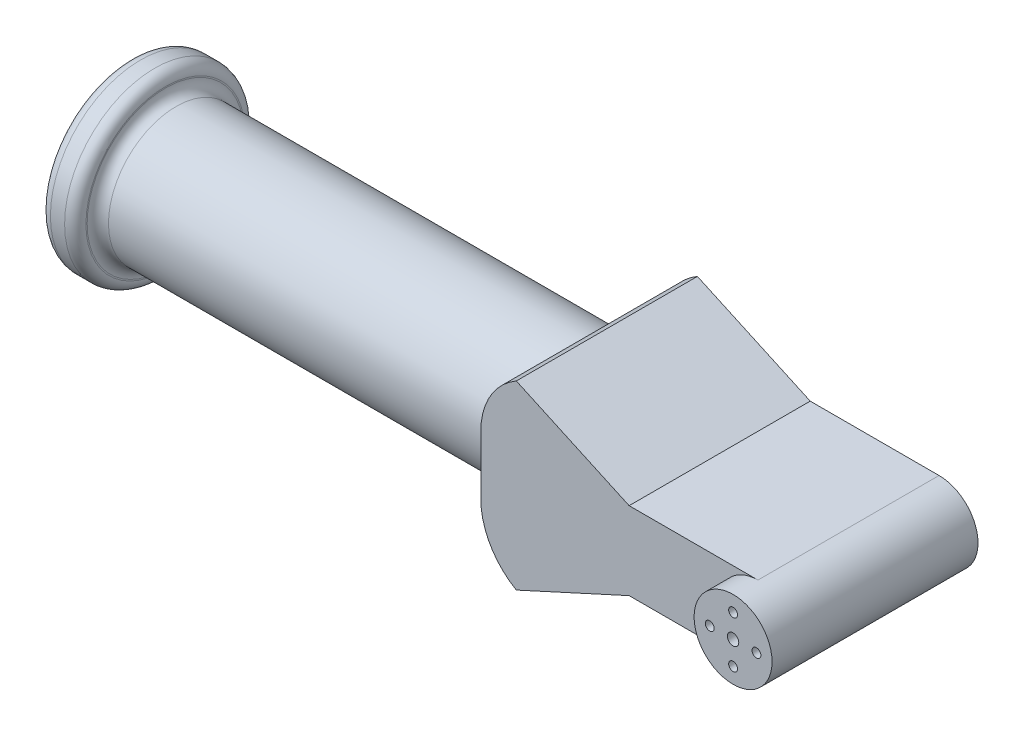
SolidWorks part; units mm, degrees
ref_plane "Front Plane" through (0, 0, 0) normal (0, 0, 1) x (1, 0, 0)
ref_plane "Top Plane" through (0, 0, 0) normal (0, 1, 0) x (1, 0, 0)
ref_plane "Right Plane" through (0, 0, 0) normal (1, 0, 0) x (0, 0, -1)
sketch "Sketch1" plane through (0, 0, 0) normal (1, 0, 0) x (0, 0, -1)
  line L0 (0, 10.97) -> (80, 10.97)
  line L1 (80, 10.97) -> (80, -10.97)
  line L2 (0, -10.97) -> (80, -10.97)
  arc A0 (0, 10.97) -> (0, -10.97) centre (0, 0) ccw
  dimension "D1" = 21.94
  dimension "D2" = 80
extrude "Boss-Extrude1" add sketch "Sketch1" along normal blind 15
sketch "Sketch2" plane through (15, 0, 0) normal (1, 0, 0) x (0, 0, -1)
  line L0 (0, 28.05) -> (0, -28.05) construction
  circle A0 centre (0, 0) radius 10.97
  circle A1 centre (0, 0) radius 1.6
  circle A2 centre (0, 6.58) radius 1.25
  circle A3 centre (6.58, 0) radius 1.25
  circle A4 centre (0, -6.58) radius 1.25
  circle A5 centre (-6.58, 0) radius 1.25
  point P17 (0, 0)
  dimension "D1" = 3.2
  dimension "D2" = 2.5
  dimension "D3" = 6.58
  dimension "D4" = 4
extrude "Boss-Extrude2" add sketch "Sketch2" along normal blind 5.89
sketch "Sketch3" plane through (20.89, 0, 0) normal (1, 0, 0) x (0, 0, -1)
  circle A0 centre (0, 6.58) radius 1.25
  circle A1 centre (0, 0) radius 1.6
  circle A2 centre (0, -6.58) radius 1.25
  circle A3 centre (-6.58, 0) radius 1.25
  circle A4 centre (6.58, 0) radius 1.25
extrude "Cut-Extrude1" cut sketch "Sketch3" against normal blind 100
sketch "Sketch4" plane through (15, 0, 0) normal (1, 0, 0) x (0, 0, -1)
  line L0 (80, 10.97) -> (0, 10.97) construction
  line L1 (30, 10.97) -> (80, 10.97)
  line L2 (30, 10.97) -> (30, -10.97)
  line L3 (30, -10.97) -> (80, -10.97)
  line L4 (80, 10.97) -> (80, -10.97)
  dimension "D1" = 30
extrude "Boss-Extrude3" add sketch "Sketch4" along normal blind 49.02
sketch "Sketch5" plane through (0, 0, 0) normal (0, 1, 0) x (1, 0, 0)
  line L0 (0, -12.067) -> (0, 12.067) construction
  line L1 (64.02, 34.7595) -> (0, 34.7595) construction
  line L2 (64.02, 80) -> (64.02, 30) construction
  line L3 (32.01, 80) -> (32.01, -10.8477) construction
  line L4 (64.02, 80) -> (0, 80) construction
sketch "Sketch6" plane through (0, 10.97, 0) normal (0, 1, 0) x (1, 0, 0)
  line L0 (64.02, 80) -> (0, 80) construction
  line L1 (15, 30) -> (44, 30)
  line L2 (15, 30) -> (15, 80)
  line L3 (15, 80) -> (44, 80)
  line L4 (44, 30) -> (44, 80)
sketch "Sketch9" plane through (0, 0, 0) normal (-1, 0, 0) x (0, 0, 1)
  line L0 (-80, 0) -> (10.8477, 0) construction
  line L1 (-80, 25.5) -> (-29, 25.5)
  line L2 (-80, 25.5) -> (-80, -25.5)
  line L3 (-80, -25.5) -> (-29, -25.5)
  line L4 (-29, 25.5) -> (-29, -25.5)
  line L5 (-80, 25.5) -> (-29, -25.5) construction
  line L6 (-80, -25.5) -> (-29, 25.5) construction
  line L7 (-80, 10.97) -> (-80, -10.97) construction
  point P0 (-54.5, 0)
  dimension "D1" = 29
  dimension "D2" = 25.5
  dimension "D3" = 0
extrude "Boss-Extrude7" add sketch "Sketch9" along normal blind 10
sketch "Sketch10" plane through (-10, 0, 0) normal (-1, 0, 0) x (0, 0, 1)
  line L0 (-80, 0) -> (-29, 0) construction
  line L1 (-80, 10.97) -> (-80, -10.97) construction
  line L2 (-29, -25.5) -> (-29, 25.5) construction
  circle A0 centre (-54.5, 0) radius 19.05
  dimension "D1" = 38.1
extrude "Boss-Extrude8" add sketch "Sketch10" along normal blind 114.3
sketch "Sketch11" plane through (-124.3, 0, 0) normal (-1, 0, 0) x (0, 0, 1)
  line L0 (-73.55, 0) -> (-35.45, 0) construction
  line L1 (-80, 0) -> (10.8477, 0) construction
  circle A0 centre (-54.5, 0) radius 19.05 construction
  circle A1 centre (-54.5, 0) radius 25.4
  dimension "D1" = 50.8
extrude "Boss-Extrude9" add sketch "Sketch11" along normal blind 10
sketch "Sketch12" plane through (0, 0, -30) normal (0, 0, 1) x (1, 0, 0)
  line L0 (64.02, -10.97) -> (15, -10.97) construction
  line L1 (64.02, 10.97) -> (49.02, 10.97)
  line L2 (64.02, 10.97) -> (64.02, -10.97)
  line L3 (64.02, -10.97) -> (49.02, -10.97)
  line L4 (49.02, 10.97) -> (49.02, -10.97)
  dimension "D1" = 15
extrude "Boss-Extrude10" add sketch "Sketch12" along normal blind 30
sketch "Sketch13" plane through (64.02, 0, 0) normal (1, 0, 0) x (0, 0, -1)
  circle A0 centre (0, 0) radius 10.97
  circle A1 centre (0, 0) radius 1.6
  circle A2 centre (6.58, 0) radius 1.25
  circle A3 centre (0, 6.58) radius 1.25
  circle A4 centre (0, -6.58) radius 1.25
  circle A5 centre (-6.58, 0) radius 1.25
  point P17 (0, 0)
  dimension "D1" = 4
extrude "Boss-Extrude11" add sketch "Sketch13" against normal blind 20.89
sketch "Sketch15" plane through (64.02, 0, 0) normal (1, 0, 0) x (0, 0, -1)
  circle A0 centre (0, 0) radius 1.6
  circle A1 centre (0, 6.58) radius 1.25
  circle A2 centre (6.58, 0) radius 1.25
  circle A3 centre (0, -6.58) radius 1.25
  circle A4 centre (-6.58, 0) radius 1.25
  point P15 (0, 0)
  dimension "D1" = 4
extrude "Cut-Extrude2" cut sketch "Sketch15" against normal blind 20.89
sketch "Sketch17" plane through (0, 0, 0) normal (1, 0, 0) x (0, 0, -1)
  line L1 (29, 25.5) -> (80, 25.5)
  line L2 (29, 25.5) -> (29, -25.5)
  line L3 (29, -25.5) -> (80, -25.5)
  line L4 (80, 25.5) -> (80, -25.5)
extrude "Boss-Extrude12" add sketch "Sketch17" along normal blind 79.02
sketch "Sketch18" plane through (0, 0, -29) normal (0, 0, 1) x (1, 0, 0)
  line L1 (39.5513, 13.4042) -> (70.044, 13.4042)
  line L2 (39.5513, 13.4042) -> (39.5513, -17.0884)
  line L3 (39.5513, -17.0884) -> (70.044, -17.0884)
  line L4 (70.044, 13.4042) -> (70.044, -17.0884)
extrude "Cut-Extrude3" cut sketch "Sketch18" along normal blind 64
sketch "Sketch19" plane through (0, 0, -29) normal (0, 0, 1) x (1, 0, 0)
  line L0 (79.02, 25.5) -> (79.02, -25.5) construction
  line L1 (79.02, 10.97) -> (64.02, 10.97)
  line L2 (79.02, 10.97) -> (79.02, -10.97)
  line L3 (79.02, -10.97) -> (64.02, -10.97)
  line L4 (64.02, 10.97) -> (64.02, -10.97)
  line L5 (50.0335, 0) -> (-50.0335, 0) construction
  dimension "D1" = 15
  dimension "D2" = 21.94
  dimension "D3" = 10.97
extrude "Boss-Extrude13" add sketch "Sketch19" along normal blind 29
sketch "Sketch20" plane through (79.02, 0, 0) normal (1, 0, 0) x (0, 0, -1)
  circle A0 centre (0, 0) radius 10.97
  circle A1 centre (0, 0) radius 1.6
  circle A2 centre (0, 6.58) radius 1.25
  circle A3 centre (6.58, 0) radius 1.25
  circle A4 centre (0, -6.58) radius 1.25
  circle A5 centre (-6.58, 0) radius 1.25
  point P17 (0, 0)
  dimension "D1" = 4
extrude "Boss-Extrude14" add sketch "Sketch20" against normal blind 20.98
sketch "Sketch21" plane through (79.02, 0, 0) normal (1, 0, 0) x (0, 0, -1)
  circle A0 centre (0, 0) radius 1.6
  circle A1 centre (0, 6.58) radius 1.25
  circle A2 centre (6.58, 0) radius 1.25
  circle A3 centre (0, -6.58) radius 1.25
  circle A4 centre (-6.58, 0) radius 1.25
  point P14 (0, 0)
  dimension "D1" = 4
extrude "Cut-Extrude4" cut sketch "Sketch21" against normal blind 20.98
sketch "Sketch23" plane through (79.02, 0, 0) normal (1, 0, 0) x (0, 0, -1)
  line L0 (29, -10.97) -> (29, -25.5) construction
  line L1 (-13.4821, 15.5896) -> (29, 15.5896)
  line L2 (-13.4821, 15.5896) -> (-13.4821, -18.235)
  line L3 (-13.4821, -18.235) -> (29, -18.235)
  line L4 (29, 15.5896) -> (29, -18.235)
extrude "Cut-Extrude6" cut sketch "Sketch23" against normal blind 100
sketch "Sketch27" plane through (0, 0, -29) normal (0, 0, 1) x (1, 0, 0)
  line L1 (44, 0) -> (-44, 0) construction
  line L2 (25.67, 18.75) -> (52.37, 18.75)
  line L3 (25.67, 18.75) -> (25.67, -18.75)
  line L4 (25.67, -18.75) -> (52.37, -18.75)
  line L5 (52.37, 18.75) -> (52.37, -18.75)
  line L6 (25.67, 18.75) -> (52.37, -18.75) construction
  line L7 (25.67, -18.75) -> (52.37, 18.75) construction
  line L8 (79.02, 25.5) -> (79.02, -25.5) construction
  point P2 (39.02, 0)
  dimension "D1" = 26.7
  dimension "D2" = 37.5
  dimension "D3" = 40
sketch "Sketch24" plane through (0, 25.5, 0) normal (0, 1, 0) x (1, 0, 0)
  line L0 (-10, 54.5) -> (79.02, 54.5) construction
  line L1 (-10, 29) -> (-10, 80) construction
  line L2 (79.02, 80) -> (79.02, 29) construction
  circle A0 centre (34.51, 54.5) radius 1.6
  circle A1 centre (34.51, 61.08) radius 1.25
  circle A2 centre (41.09, 54.5) radius 1.25
  circle A3 centre (34.51, 47.92) radius 1.25
  circle A4 centre (27.93, 54.5) radius 1.25
  dimension "D1" = 3.2
  dimension "D2" = 2.5
  dimension "D3" = 6.58
  dimension "D4" = 4
sketch "Sketch31" plane through (0, 25.5, 0) normal (0, 1, 0) x (1, 0, 0)
  line L0 (-28.05, 0) -> (28.05, 0) construction
  line L1 (-10, 80) -> (40.8, 80)
  line L2 (-10, 80) -> (-10, 0)
  line L3 (-10, 0) -> (40.8, 0)
  line L4 (40.8, 80) -> (40.8, 0)
  dimension "D1" = 50.8
sketch "Sketch32" plane through (0, 25.5, 0) normal (0, 1, 0) x (1, 0, 0)
  line L0 (-10, 80) -> (79.02, 80) construction
  line L1 (79.02, 29) -> (40.8, 29)
  line L2 (79.02, 29) -> (79.02, 80)
  line L3 (79.02, 80) -> (40.8, 80)
  line L4 (40.8, 29) -> (40.8, 80)
sketch "Sketch38" plane through (-10, 0, 0) normal (-1, 0, 0) x (0, 0, 1)
  line L0 (-80, -25.5) -> (-10.8, -25.5) construction
  line L5 (-80, 25.5) -> (-53.9876, 25.5)
  line L6 (-80, 25.5) -> (-80, -25.5)
  line L7 (-80, -25.5) -> (-53.9876, -25.5)
  line L8 (-53.9876, 25.5) -> (-53.9876, -25.5)
  circle A2 centre (-53.9876, 0) radius 25.5
fillet "Fillet6" radius 3 2 edges at (-124.3, 0, -29.1) (-124.3, 0, -35.45)
fillet "Fillet7" radius 3 1 edges at (-134.3, 0, -29.1)
sketch "Sketch40" plane through (0, 25.5, 0) normal (0, 1, 0) x (1, 0, 0)
  line L0 (0, -28.05) -> (0, 28.05) construction
  line L1 (79.02, 80) -> (0, 80)
  line L2 (79.02, 80) -> (79.02, 39)
  line L3 (79.02, 39) -> (0, 39)
  line L4 (0, 80) -> (0, 39)
  line L6 (79.02, 29) -> (40.8, 29) construction
  dimension "D1" = 10
sketch "Sketch41" plane through (0, 0, -29) normal (0, 0, 1) x (1, 0, 0)
  line L0 (28.05, 0) -> (-28.05, 0) construction
  line L1 (79.02, 25.5) -> (79.02, -25.5) construction
  line L2 (0, -28.05) -> (0, 28.05) construction
  line L3 (-10, 25.5) -> (79.02, 25.5)
  line L4 (-10, 25.5) -> (-10, -25.5)
  line L5 (-10, -25.5) -> (79.02, -25.5)
  line L6 (79.02, 25.5) -> (79.02, -25.5)
  line L7 (0, 25.5) -> (79.02, 25.5)
  line L8 (0, 25.5) -> (0, -25.5)
  line L9 (0, -25.5) -> (79.02, -25.5)
  line L10 (79.02, 25.5) -> (79.02, -25.5)
  line L11 (0, -25.5) -> (31.7741, -10.97)
  line L12 (0, 25.5) -> (31.7741, 10.97)
  line L13 (68.05, 10.97) -> (31.7741, 10.97)
  line L15 (31.7741, -10.97) -> (68.05, -10.97)
  circle A0 centre (68.05, 0) radius 10.97
  circle A1 centre (68.05, 0) radius 1.6
  circle A2 centre (68.05, 6.58) radius 1.25
  circle A3 centre (74.63, 0) radius 1.25
  circle A4 centre (68.05, -6.58) radius 1.25
  circle A5 centre (61.47, 0) radius 1.25
  line M11 (79.02, -25.5) -> (79.02, 25.5)
  line M12 (79.02, 25.5) -> (-10, 25.5)
  dimension "D1" = 21.94
  dimension "D3" = 3.2
  dimension "D4" = 2.5
  dimension "D2" = 10.97
  dimension "D5" = 6.58
  dimension "D6" = 4
extrude "Cut-Extrude16" cut sketch "Sketch41" against normal blind 100 contours A0 L15 L11 L5 M11 | A0 L10 L12 L13 M12 | A4 | A1 | A5 | A2 | A3 region at (47.6027, 18.5617, -29) region at (47.6027, -18.5617, -29) region at (68.05, 0, -29) region at (68.05, 6.58, -29) region at (74.63, 0, -29) region at (68.05, -6.58, -29) region at (61.47, 0, -29)
sketch "Sketch44" plane through (0, 0, -29) normal (0, 0, 1) x (1, 0, 0)
  circle A0 centre (68.05, 0) radius 10.97
  circle A1 centre (68.05, 0) radius 1.6
  circle A2 centre (74.63, 0) radius 1.25
  circle A3 centre (68.05, -6.58) radius 1.25
  circle A4 centre (61.47, 0) radius 1.25
  circle A5 centre (68.05, 6.58) radius 1.25
  dimension "D1" = 4
extrude "Boss-Extrude18" add sketch "Sketch44" along normal blind 7
fillet "Fillet9" radius 20 1 edges at (-10, 25.5, -54.5)
fillet "Fillet10" radius 20 1 edges at (-10, -25.5, -54.5)
